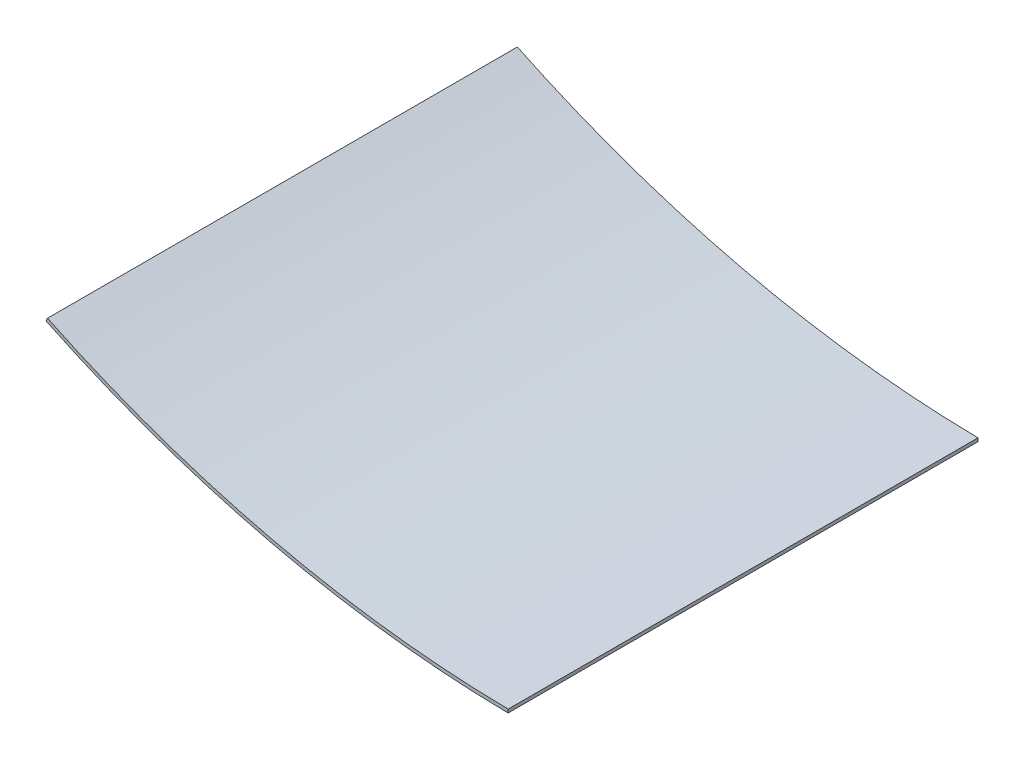
SolidWorks part; units mm, degrees
material "Acrylic (Medium-high impact)"
ref_plane "Front Plane" through (0, 0, 0) normal (0, 0, 1) x (1, 0, 0)
ref_plane "Top Plane" through (0, 0, 0) normal (0, 1, 0) x (1, 0, 0)
ref_plane "Right Plane" through (0, 0, 0) normal (1, 0, 0) x (0, 0, -1)
sketch "Sketch1" plane through (0, 0, 0) normal (0, 0, 1) x (1, 0, 0)
  line L0 (-426.0964, 298.5925) -> (-427.4709, 295.7304)
  line L1 (0, 198.54) -> (-0.043, 195.3653)
  arc A0 (-426.0964, 298.5925) -> (0, 198.54) centre (13.752, 1214.4469) ccw construction
  arc A1 (-426.0964, 298.5925) -> (0, 198.54) centre (13.752, 1214.4469) ccw
  arc A2 (-427.4709, 295.7304) -> (-0.043, 195.3653) centre (13.752, 1214.4469) ccw
  dimension "D1" = 3.175
extrude "Boss-Extrude1" add sketch "Sketch1" against normal up to surface (434.6 mm away)
